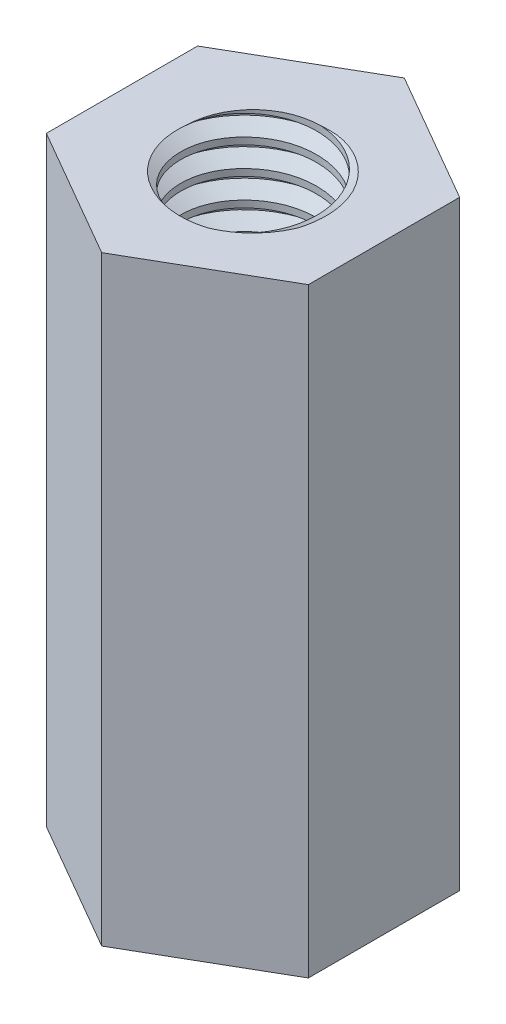
SolidWorks part; units mm, degrees
ref_plane "Front Plane" through (0, 0, 0) normal (0, 0, 1) x (1, 0, 0)
ref_plane "Top Plane" through (0, 0, 0) normal (0, 1, 0) x (1, 0, 0)
ref_plane "Right Plane" through (0, 0, 0) normal (1, 0, 0) x (0, 0, -1)
sketch "Sketch1" plane through (0, 0, 0) normal (0, 1, 0) x (1, 0, 0)
  line L1 (2.4, 1.3856) -> (0, 2.7713)
  line L2 (0, 2.7713) -> (-2.4, 1.3856)
  line L3 (-2.4, 1.3856) -> (-2.4, -1.3856)
  line L4 (-2.4, -1.3856) -> (0, -2.7713)
  line L5 (0, -2.7713) -> (2.4, -1.3856)
  line L6 (2.4, -1.3856) -> (2.4, 1.3856)
  circle A0 centre (0, 0) radius 2.4 construction
  circle A1 centre (0, 0) radius 1.25
  dimension "D1" = 4.8
  dimension "D2" = 2.5
extrude "Boss-Extrude1" add sketch "Sketch1" along normal blind 11
thread "Thread1" pitch 0.5 method cut profile "Thread Profile1" start angle 0, offset 2, length 22, pitch 0.5, diameter 2.5
ref_plane "Plane1" through (-1.25, 13, 0) normal (0, 0, 1) x (-1, 0, 0)
sketch "Thread Profile1" plane through (-1.25, 13, 0) normal (0, 0, 1) x (-1, 0, 0)
  line L0 (0, 0) -> (0, 0.5) construction
  line L1 (0, 0) -> (0.2706, 0.1562)
  line L2 (0.2706, 0.1562) -> (0.2706, 0.2187)
  line L3 (0.2706, 0.2187) -> (0, 0.375)
  line L4 (0.2706, 0.1875) -> (0, 0.1875) construction
  line L11 (0, 0) -> (0, 0.375)
  point P2 (0, 0)
  dimension "Pitch" = 0.5
  dimension "Profile_Angle" = 60
  dimension "Profile_Land" = 0.0625
  dimension "Profile_Height" = 0.2706
